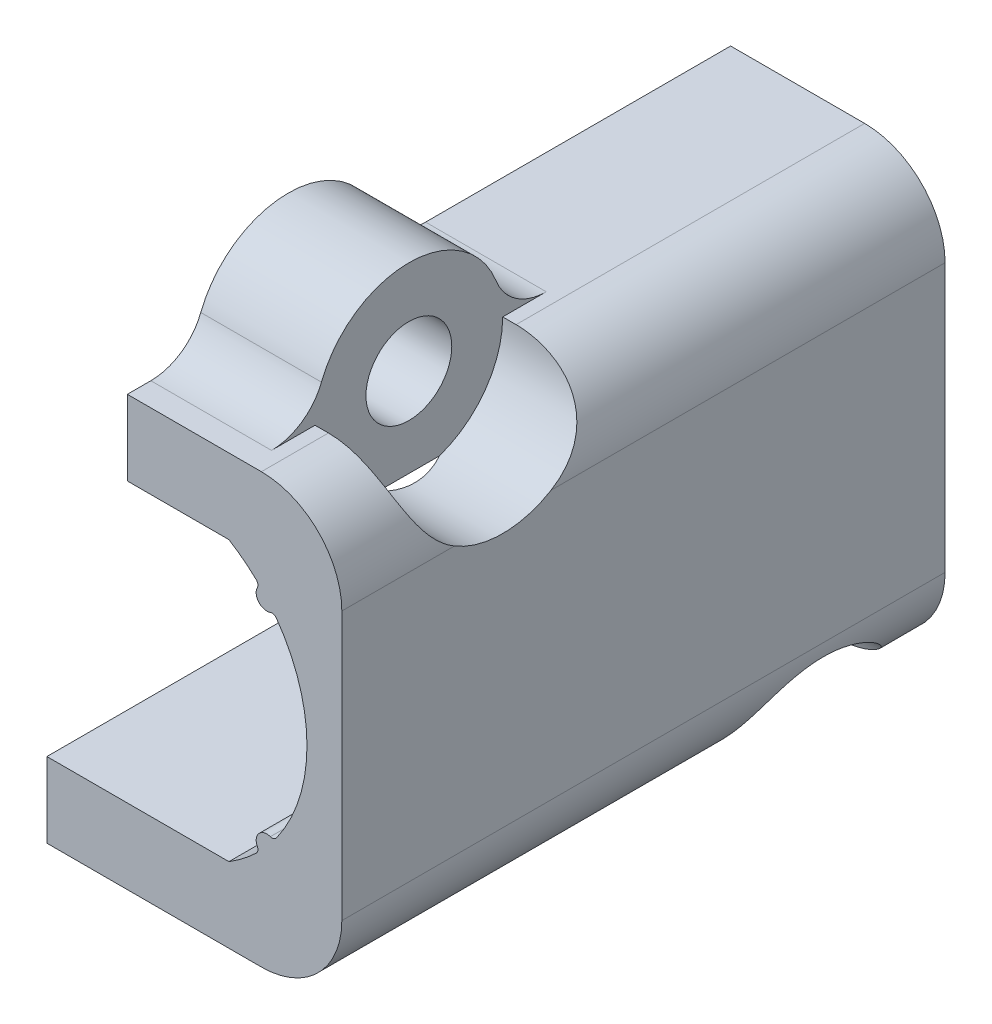
SolidWorks part; units mm, degrees
ref_plane "前视基准面" through (0, 0, 0) normal (0, 0, 1) x (1, 0, 0)
ref_plane "上视基准面" through (0, 0, 0) normal (0, 1, 0) x (1, 0, 0)
ref_plane "右视基准面" through (0, 0, 0) normal (1, 0, 0) x (0, 0, -1)
other "Configuration Table"
sketch "草图1" plane through (0, 0, 0) normal (0, 1, 0) x (1, 0, 0)
  line L1 (0, 0) -> (8, 0)
  line L2 (0, 0) -> (0, 20)
  line L3 (0, 20) -> (8, 20)
  line L4 (8, 0) -> (8, 20)
  line L5 (0, 0) -> (8, 20) construction
  line L6 (0, 20) -> (8, 0) construction
  point P4 (4, 10)
  dimension "D1" = 8
  dimension "D2" = 20
extrude "凸台-拉伸1" add sketch "草图1" along normal blind 16
sketch "草图2" plane through (0, 0, 0) normal (0, 0, 1) x (1, 0, 0)
  line L0 (0, 16) -> (0, 0) construction
  line L1 (0, 2.8) -> (6.8, 2.8)
  line L2 (0, 2.8) -> (0, 13.2)
  line L3 (0, 13.2) -> (6.8, 13.2)
  line L4 (6.8, 2.8) -> (6.8, 13.2)
  line L5 (0, 2.8) -> (6.8, 13.2) construction
  line L6 (0, 13.2) -> (6.8, 2.8) construction
  line L7 (8, 8) -> (3.4, 8) construction
  line L8 (8, 16) -> (8, 0) construction
  point P4 (3.4, 8)
  dimension "D1" = 6.8
  dimension "D2" = 10.4
extrude "切除-拉伸1" cut sketch "草图2" against normal up to next
sketch "草图3" plane through (0, 0, 0) normal (0, 0, 1) x (1, 0, 0)
  line L1 (0.6, 8) -> (8, 8) construction
  line L2 (8, 16) -> (8, 0) construction
  line L3 (3.789, 13.2) -> (6.8, 13.2)
  line L4 (6.8, 13.2) -> (0, 13.2) construction
  line L5 (6.8, 13.2) -> (6.8, 2.8)
  line L6 (6.8, 2.8) -> (3.789, 2.8)
  line L8 (0, 2.8) -> (6.8, 2.8) construction
  arc A0 (3.789, 2.8) -> (3.789, 13.2) centre (0.6, 8) ccw
  dimension "D1" = 12.2
  dimension "D2" = 6.2
extrude "凸台-拉伸3" add sketch "草图3" against normal offset from surface (10.8 mm away) 9.2 up to face at (3.7, 8, -20)
sketch "草图4" plane through (8, 0, 0) normal (1, 0, 0) x (0, 0, -1)
  line L0 (0, 8) -> (20, 8) construction
  line L1 (0, 16) -> (0, 0) construction
  line L2 (20, 16) -> (20, 0) construction
  circle A0 centre (4, 16) radius 1.6
  circle A1 centre (16, -1) radius 1.6
  dimension "D1" = 8
  dimension "D2" = 16
  dimension "D3" = 3.2
  dimension "D4" = 4
  dimension "D5" = 9
extrude "切除-拉伸2" cut sketch "草图4" against normal up to next
sketch "草图6" plane through (0, 0, 0) normal (-1, 0, 0) x (0, 0, 1)
  line L5 (-20, 0) -> (-17.249, 0)
  line L6 (-14.751, 0) -> (0, 0)
  line L7 (0, 0) -> (0, 2.8)
  line L8 (0, 2.8) -> (-20, 2.8)
  line L9 (-20, 2.8) -> (-20, 0)
  line L10 (-20, 0) -> (-17.249, 0)
  line L11 (-14.751, 0) -> (0, 0)
  line L12 (0, 0) -> (0, 2.8)
  line L13 (0, 2.8) -> (-20, 2.8)
  line L14 (-20, 2.8) -> (-20, 0)
  arc A1 (-14.751, 0) -> (-17.249, 0) centre (-16, -1) ccw
  arc A2 (-14.751, 0) -> (-17.249, 0) centre (-16, -1) ccw
  dimension "D1" = 0
extrude "凸台-拉伸5" add sketch "草图6" along normal blind 3
sketch "草图5" plane through (0, 0, 0) normal (-1, 0, 0) x (0, 0, 1)
  line L0 (-6.1, 13.2) -> (-1.9, 13.2)
  line L1 (-20, 13.2) -> (0, 13.2) construction
  circle A0 centre (-4, 16) radius 1.6
  arc A2 (-1.9, 13.2) -> (-6.1, 13.2) centre (-4, 16) ccw
  dimension "D2" = 7
extrude "凸台-拉伸4" add sketch "草图5" against normal blind 4.5
sketch "草图7" plane through (-3, 0, 0) normal (-1, 0, 0) x (0, 0, 1)
  circle A0 centre (-16, -1) radius 1.6
  circle A1 centre (-16, -1) radius 3.5
  dimension "D1" = 7
extrude "凸台-拉伸6" add sketch "草图7" against normal blind 3
sketch "草图8" plane through (0, 0, 0) normal (1, 0, 0) x (0, 0, -1)
  circle A0 centre (16, -1) radius 3.5
extrude "切除-拉伸3" cut sketch "草图8" along normal up to next
sketch "草图9" plane through (0, 0, -20) normal (0, 0, -1) x (-1, 0, 0)
  line L8 (-6.8, 2.8) -> (-6.8, 13.2)
  line L9 (-6.8, 13.2) -> (0, 13.2)
  line L10 (0, 13.2) -> (0, 16)
  line L11 (0, 16) -> (-8, 16)
  line L12 (-8, 16) -> (-8, 0)
  line L13 (-8, 0) -> (3, 0)
  line L14 (3, 0) -> (3, 2.8)
  line L15 (3, 2.8) -> (-6.8, 2.8)
  line L16 (-6.8, 2.8) -> (-6.8, 13.2)
  line L17 (-6.8, 13.2) -> (0, 13.2)
  line L18 (0, 13.2) -> (0, 16)
  line L19 (0, 16) -> (-8, 16)
  line L20 (-8, 16) -> (-8, 0)
  line L21 (-8, 0) -> (3, 0)
  line L22 (3, 0) -> (3, 2.8)
  line L23 (3, 2.8) -> (-6.8, 2.8)
  dimension "D1" = 0
extrude "凸台-拉伸7" add sketch "草图9" along normal blind 0.5
sketch "草图10" plane through (4.5, 0, 0) normal (1, 0, 0) x (0, 0, -1)
  circle A0 centre (4, 16) radius 3.5
extrude "切除-拉伸4" cut sketch "草图10" along normal up to next
sketch "草图11" plane through (0, 0, 0) normal (0, 0, 1) x (1, 0, 0)
  line L7 (0, 13.2) -> (3.789, 13.2)
  line L8 (3.789, 2.8) -> (-3, 2.8)
  line L9 (-3, 2.8) -> (-3, 0)
  line L10 (-3, 0) -> (8, 0)
  line L11 (8, 0) -> (8, 16)
  line L12 (8, 16) -> (0, 16)
  line L13 (0, 16) -> (0, 13.2)
  line L14 (0, 13.2) -> (3.789, 13.2)
  line L15 (3.789, 2.8) -> (-3, 2.8)
  line L16 (-3, 2.8) -> (-3, 0)
  line L17 (-3, 0) -> (8, 0)
  line L18 (8, 0) -> (8, 16)
  line L19 (8, 16) -> (0, 16)
  line L20 (0, 16) -> (0, 13.2)
  arc A1 (3.789, 2.8) -> (3.789, 13.2) centre (0.6, 8) ccw
  arc A2 (3.789, 2.8) -> (3.789, 13.2) centre (0.6, 8) ccw
  dimension "D1" = 0
extrude "凸台-拉伸8" add sketch "草图11" along normal blind 2
fillet "圆角1" radius 2 2 edges at (2.25, 16, -0.5) (-1.5, 0, -19.3541)
fillet "圆角2" radius 3 2 edges at (8, 16, 0.75) (8, 0, -19.9271)
sketch "草图12" plane through (6.8, 0, 0) normal (-1, 0, 0) x (0, 0, 1)
  line L4 (-10.8, 2.8) -> (-10.8, 13.2)
  line L5 (-10.8, 13.2) -> (-20.5, 13.2)
  line L6 (-20.5, 13.2) -> (-20.5, 2.8)
  line L7 (-20.5, 2.8) -> (-10.8, 2.8)
  line L8 (-10.8, 2.8) -> (-10.8, 13.2)
  line L9 (-10.8, 13.2) -> (-20.5, 13.2)
  line L10 (-20.5, 13.2) -> (-20.5, 2.8)
  line L11 (-20.5, 2.8) -> (-10.8, 2.8)
  dimension "D1" = 0
extrude "凸台-拉伸9" add sketch "草图12" along normal blind 0.6
sketch "草图13" plane through (0, 0, 2) normal (0, 0, 1) x (1, 0, 0)
  line L0 (0.6, 8) -> (6.7, 8) construction
  circle A0 centre (5.2054, 12) radius 0.4
  arc A1 (3.789, 2.8) -> (3.789, 13.2) centre (0.6, 8) ccw construction
  circle A2 centre (5.2054, 4) radius 0.4
  dimension "D1" = 0.8
  dimension "D2" = 4
extrude "凸台-拉伸10" add sketch "草图13" against normal up to surface (12.8 mm away) up to face at (5.4679, 12.335, -10.8)
fillet "圆角3" radius 0.2 4 edges at (4.9334, 12.2932, -4.4) (5.4577, 11.6896, -4.4) (5.4577, 4.3104, -4.4) (4.9334, 3.7068, -4.4)
sketch "草图14" plane through (-3, 0, 0) normal (-1, 0, 0) x (0, 0, 1)
  line L0 (-10.8, 13.2) -> (-20.5, 13.2) construction
  line L1 (-20.5, 8) -> (-10.8, 8) construction
  line L2 (-20.5, 13.2) -> (-20.5, 2.8) construction
  line L3 (-10.8, 5.5813) -> (-10.8, 10.4187) construction
  circle A0 centre (-15.65, 13.2) radius 0.3
  circle A1 centre (-15.65, 2.8) radius 0.3
  dimension "D1" = 0.6
extrude "凸台-拉伸11" add sketch "草图14" against normal up to surface (9.2 mm away) up to face at (6.2, 8, -14.0333)
sketch "草图15" plane through (-3, 0, 0) normal (-1, 0, 0) x (0, 0, 1)
  circle A1 centre (-15.65, 13.2) radius 0.3
  circle A2 centre (-15.65, 13.2) radius 0.3
  dimension "D1" = 0
extrude "切除-拉伸5" cut sketch "草图15" against normal up to surface (3 mm away) up to face at (0, 15.3297, -8.43)
fillet "圆角4" radius 0.2 3 edges at (1.6, 2.8, -15.35) (1.6, 2.8, -15.95) (3.1, 13.2, -15.35)
